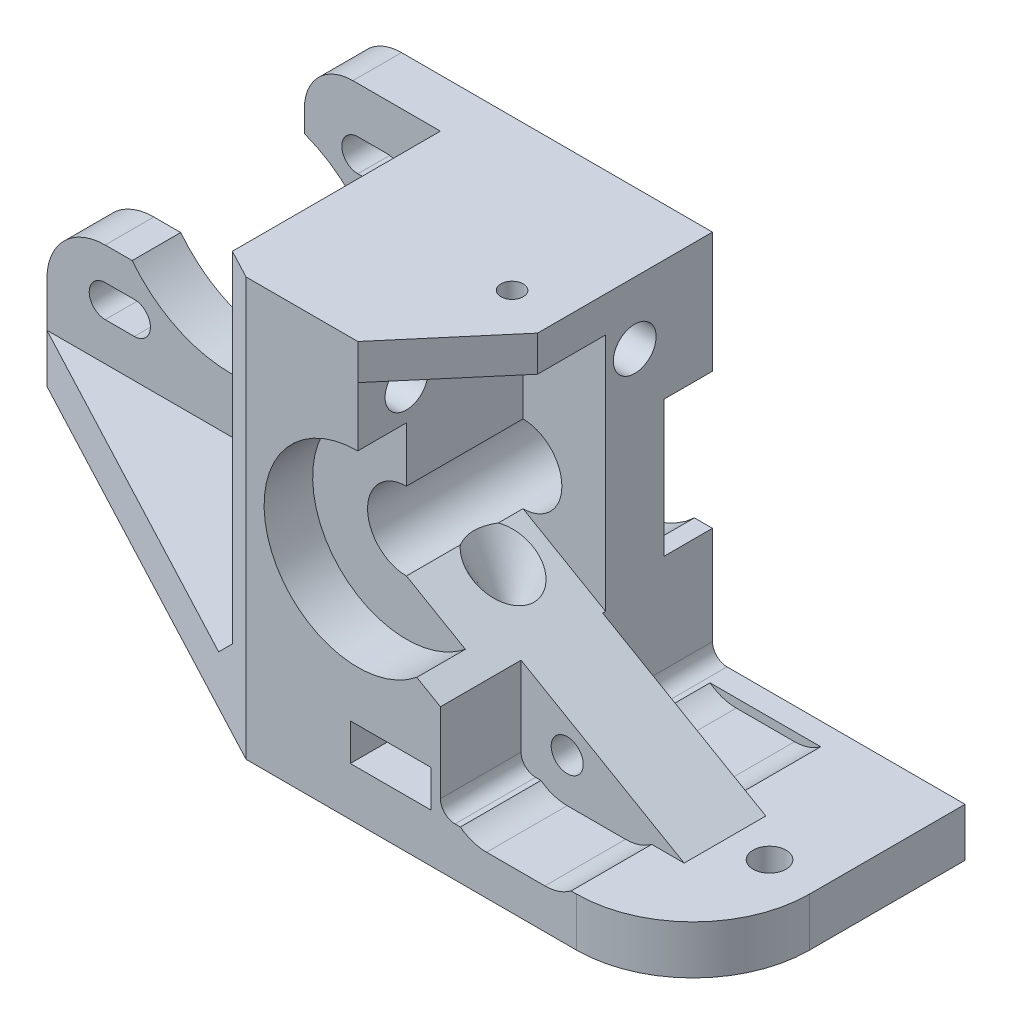
SolidWorks part; units mm, degrees
ref_plane "Front Plane" through (0, 0, 0) normal (0, 0, 1) x (1, 0, 0)
ref_plane "Top Plane" through (0, 0, 0) normal (0, 1, 0) x (1, 0, 0)
ref_plane "Right Plane" through (0, 0, 0) normal (1, 0, 0) x (0, 0, -1)
sketch "Sketch1" plane through (0, 0, 0) normal (0, 0, 1) x (1, 0, 0)
  line L0 (0, 0) -> (-60, 0) construction
  line L1 (-55, -23.6) -> (34.5, -23.6)
  line L2 (-55, -23.6) -> (-55, -8)
  line L3 (-28.5, 19.4) -> (34.5, 19.4)
  line L4 (34.5, -23.6) -> (34.5, 19.4)
  line L5 (-34.5, 0) -> (-34.5, -23.6) construction
  line L6 (-21.5, -17.6494) -> (-21.5, 14.65) construction
  line L7 (-20, 13) -> (-50, 13) construction
  line L8 (-23, 11.35) -> (-20, 11.35)
  line L9 (-23, 11.35) -> (-23, 14.65) construction
  line L10 (-23, 14.65) -> (-20, 14.65)
  line L11 (-20, 11.35) -> (-20, 14.65) construction
  line L12 (-36, -12.9851) -> (-33, -12.9851)
  line L14 (-20, -11.35) -> (-20, -14.65) construction
  line L15 (-23, -14.65) -> (-20, -14.65)
  line L16 (-23, -11.35) -> (-23, -14.65) construction
  line L17 (-23, -11.35) -> (-20, -11.35)
  line L18 (-46, -11.35) -> (-49, -11.35)
  line L19 (-46, -11.35) -> (-46, -14.65) construction
  line L20 (-46, -14.65) -> (-49, -14.65)
  line L21 (-49, -11.35) -> (-49, -14.65) construction
  line L26 (-28.5, 19.4) -> (-28.5, 12.1804)
  line L27 (-55, -8) -> (-46.228, -8)
  line L28 (-50, -13) -> (-19, -13) [skipped]
  line L29 (-47.5, 17.6494) -> (-47.5, -13.3506) [skipped]
  circle A0 centre (0, 0) radius 4
  circle A1 centre (-34.5, 0) radius 13 construction
  arc A2 (-46.228, -8) -> (-36, -12.9851) centre (-36, 0) ccw
  arc A3 (-20, 11.35) -> (-20, 14.65) centre (-20, 13) ccw
  arc A4 (-33, -12.9851) -> (-28.5, 12.1804) centre (-33, 0) ccw
  arc A5 (-23, 14.65) -> (-23, 11.35) centre (-23, 13) ccw
  arc A6 (-23, -11.35) -> (-23, -14.65) centre (-23, -13) ccw
  arc A7 (-20, -14.65) -> (-20, -11.35) centre (-20, -13) ccw
  arc A8 (-49, -11.35) -> (-49, -14.65) centre (-49, -13) ccw
  arc A9 (-46, -14.65) -> (-46, -11.35) centre (-46, -13) ccw
  dimension "D1" = 8
  dimension "D6" = 34.5
  dimension "D8" = 3.3
  dimension "D2" = 26
  dimension "D7" = 6
  dimension "D3" = 43
  dimension "D4" = 55
  dimension "D5" = 23.6
  dimension "D9" = 3
  dimension "D10" = 3
  dimension "D11" = 1.5
  dimension "D12" = 8
  dimension "D13" = 34.5
extrude "Boss-Extrude1" add sketch "Sketch1" along normal blind 28
sketch "Sketch2" plane through (0, 0, 28) normal (0, 0, 1) x (1, 0, 0)
  line L0 (-55, -8) -> (-55, -23.6) construction
  line L1 (-55, -18.6) -> (-14.5, -18.6)
  line L2 (-55, -18.6) -> (-55, 19.4)
  line L3 (-55, 19.4) -> (-14.5, 19.4)
  line L4 (-14.5, -18.6) -> (-14.5, 19.4)
  line L5 (34.5, 19.4) -> (-28.5, 19.4) construction
  line L6 (0, 0) -> (-55, 0) construction
  circle A0 centre (-34.5, 0) radius 17.3693 construction
  dimension "D1" = 20
  dimension "D2" = 18.6
  dimension "D3" = 34.5
extrude "Cut-Extrude1" cut sketch "Sketch2" against normal offset from surface (23 mm away) 5 up to face at (-21.5, -13, 0)
sketch "Sketch3" plane through (0, 0, 28) normal (0, 0, 1) x (1, 0, 0)
  circle A0 centre (0, 0) radius 9.65
  dimension "D1" = 19.3
extrude "Cut-Extrude2" cut sketch "Sketch3" against normal blind 5
ref_plane "Plane1" through (0, 0, 11) normal (0, 0, 1) x (1, 0, 0)
ref_plane "Plane2" through (0, -18.6, 0) normal (0, -1, 0) x (1, 0, 0)
ref_plane "Plane3" through (0, 0, 15.5) normal (0, 0, 1) x (1, 0, 0)
sketch "Sketch8" plane through (0, -23.6, 0) normal (0, -1, 0) x (1, 0, 0)
  circle A0 centre (3.375, 15.5) radius 1.15
  dimension "D1" = 2.3
  dimension "D2" = 3.375
  dimension "D3" = 15.5
extrude "Cut-Extrude7" cut sketch "Sketch8" against normal through all
chamfer "Chamfer1" distance 23 distance2 43.5 1 edges at (-55, -21.1, 28) first distance on face at (-55, -16.7333, 11)
sketch "Sketch9" plane through (34.5, 0, 0) normal (1, 0, 0) x (0, 0, -1)
  line L1 (-15.5, 23.65) -> (-15.5, -23.65) construction
  line L2 (0, 0) -> (-25.9492, 0) construction
  circle A0 centre (-8, 13) radius 2.2
  circle A1 centre (-23, 13) radius 2.2
  dimension "D1" = 4.4
  dimension "D2" = 7.5
  dimension "D3" = 13
  dimension "D4" = 7.5
extrude "Cut-Extrude8" cut sketch "Sketch9" against normal through all
sketch "Sketch10" plane through (-14.5, 0, 0) normal (-1, 0, 0) x (0, 0, 1)
  line L1 (5.1, 14.6743) -> (5.1, 11.3257)
  line L2 (5.1, 11.3257) -> (8, 9.6514)
  line L3 (8, 9.6514) -> (10.9, 11.3257)
  line L4 (10.9, 11.3257) -> (10.9, 14.6743)
  line L5 (10.9, 14.6743) -> (8, 16.3486)
  line L6 (8, 16.3486) -> (5.1, 14.6743)
  line L7 (25.9, 11.3257) -> (25.9, 14.6743)
  line L8 (25.9, 14.6743) -> (23, 16.3486)
  line L9 (23, 16.3486) -> (20.1, 14.6743)
  line L10 (20.1, 14.6743) -> (20.1, 11.3257)
  line L11 (20.1, 11.3257) -> (23, 9.6514)
  line L12 (23, 9.6514) -> (25.9, 11.3257)
  circle A0 centre (8, 13) radius 2.9 construction
  circle A1 centre (8, 13) radius 2.2 construction
  circle A2 centre (23, 13) radius 2.9 construction
  circle A5 centre (23, 13) radius 2.2 construction
  dimension "D1" = 5.8
extrude "Cut-Extrude9" cut sketch "Sketch10" against normal blind 4 and the other way blind 3
chamfer "Chamfer2" distance 3 angle 45 1 edges at (-14.5, -18.6, 15.7069)
sketch "Sketch16" plane through (0, 0, 28) normal (0, 0, 1) x (1, 0, 0)
  line L0 (-17.5, -18.6) -> (-55, -18.6) construction
  line L1 (34.5, 19.4) -> (8.5, 19.4)
  line L2 (34.5, 19.4) -> (34.5, -18.6)
  line L3 (34.5, -18.6) -> (8.5, -18.6)
  line L4 (8.5, 19.4) -> (8.5, -18.6)
  dimension "D1" = 8.5
extrude "Cut-Extrude12" cut sketch "Sketch16" against normal through all
sketch "Sketch4" plane through (0, 0, 0) normal (0, 0, -1) x (-1, 0, 0)
  line L0 (0, 0) -> (-36.3115, 0) construction
  line L1 (-36.3115, -7) -> (-6.6425, -7)
  line L2 (-36.3115, -7) -> (-36.3115, 7)
  line L4 (-36.3115, 7) -> (-6.6425, 7)
  line L5 (-36.3115, -7) -> (0, 5) construction
  line L6 (-1.3153, -8.4204) -> (-36.3115, 7) construction
  arc A0 (-6.6425, -7) -> (-6.6425, 7) centre (0, 0) ccw
  dimension "D1" = 19.3
  dimension "D2" = 14
extrude "Cut-Extrude3" cut sketch "Sketch4" against normal blind 5
fillet "Fillet6" radius 1.5 1 edges at (8.5, -18.6, 14)
sketch "Sketch17" plane through (0, 0, 28) normal (0, 0, 1) x (1, 0, 0)
  line L0 (8.5, 19.4) -> (8.5, 4.5686) construction
  line L1 (0, 0) -> (19.7064, 0) construction
  line L2 (0, 4) -> (0, -4) construction
  line L3 (0, 4) -> (0, 15.7335)
  line L4 (0, 15.7335) -> (8.5, 15.7335)
  line L6 (8.5, 15.7335) -> (8.5, -8.9075)
  line L7 (8.5, -8.9075) -> (0, -4)
  arc A2 (0, -4) -> (0, 4) centre (0, 0) ccw
  circle A4 centre (0, 0) radius 4 construction
  dimension "D1" = 120
extrude "Cut-Extrude13" cut sketch "Sketch17" against normal blind 17
ref_axis "Axis1" through (3.375, 19.4, 15.5) along (0, -1, 0)
sketch "Sketch20" plane through (0, 0, 15.5) normal (0, 0, 1) x (1, 0, 0)
  line L0 (3.375, -3.8) -> (3.375, -11.8) construction
  line L1 (3.375, 19.4) -> (3.375, 15.7335) construction
  line L2 (3.375, -11.8) -> (7.375, -3.8)
  line L3 (7.375, -3.8) -> (3.375, -3.8)
  line L4 (3.375, -3.8) -> (3.375, -11.8)
  dimension "D1" = 8
  dimension "D2" = 4
  dimension "D3" = 3.8
revolve "Cut-Revolve1" cut sketch "Sketch20" angle 360 about L0
sketch "Sketch21" plane through (0, 0, 15.5) normal (0, 0, 1) x (1, 0, 0)
  line L0 (14.7822, -11.8532) -> (7.25, -8.1858) construction
  line L1 (7.25, -8.1858) -> (7.25, -18.6)
  line L2 (7.25, -18.6) -> (25.2879, -18.6)
  line L3 (10, -18.6) -> (34.5, -18.6) construction
  line L4 (21.7997, -18.6) -> (15.7249, -12.5251) construction
  line L5 (6.0681, -7.5034) -> (8.5, -8.9075) construction
  line L6 (7.25, -8.1858) -> (25.2879, -18.6)
  line L7 (-15.4, -18.6) -> (15.4, -18.6) construction
  line L8 (0, -4) -> (6.0681, -7.5034) construction
  circle A0 centre (13.25, -15) radius 1.65
  arc A1 (15.7249, -12.5251) -> (14.7822, -11.8532) centre (13.25, -15) ccw construction
  point P13 (0, 0)
  dimension "D2" = 3.3
  dimension "D5" = 3.5
  dimension "D1" = 13.25
  dimension "D3" = 15
  dimension "D4" = 6
  dimension "D6" = 45
extrude "Boss-Extrude3" add sketch "Sketch21" against normal blind 4.2 and the other way blind 4.2
sketch "Sketch15" plane through (0, -23.6, 0) normal (0, -1, 0) x (1, 0, 0)
  line L0 (-20.625, 15) -> (29.375, 15) construction
  circle A1 centre (-20.625, 15) radius 1.7
  circle A2 centre (29.375, 15) radius 1.7
  circle A3 centre (3.375, 15.5) radius 1.15 construction
  point P4 (3.375, 15.5)
  dimension "D2" = 3.4
  dimension "D1" = 50
extrude "Cut-Extrude11" cut sketch "Sketch15" against normal through all
sketch "Sketch22" plane through (0, 0, 19.7) normal (0, 0, 1) x (1, 0, 0)
  line L0 (13.25, -19.5) -> (19.25, -19.5)
  line L3 (19.25, -10.5) -> (13.25, -10.5)
  arc A0 (13.25, -10.5) -> (13.25, -19.5) centre (13.25, -15) ccw
  circle A1 centre (13.25, -15) radius 1.65 construction
  arc A2 (19.25, -19.5) -> (19.25, -10.5) centre (19.25, -15) ccw
  dimension "D1" = 9
  dimension "D2" = 6
extrude "Cut-Extrude14" cut sketch "Sketch22" along normal blind 9
mirror "Mirror1" about plane through (0, 0, 15.5) normal (0, 0, 1) of "Cut-Extrude14"
chamfer "Chamfer4" distance 8.5 distance2 10 1 edges at (8.5, 17.5668, 28) first distance on face at (9.2891, -7.4521, 28)
fillet "Fillet1" radius 5 1 edges at (-28.5, 19.4, 2.5)
fillet "Fillet2" radius 6 1 edges at (-55, -8, 2.5)
fillet "Fillet4" radius 12 1 edges at (34.5, -21.1, 28)
sketch "Sketch23" plane through (0, -18.6, 0) normal (0, -1, 0) x (1, 0, 0)
  line L0 (-0.775, 28.722) -> (7.525, 28.722)
  line L3 (-0.775, 28.722) -> (-0.775, 13.104)
  line L4 (-0.775, 13.104) -> (3.375, 10.708)
  line L5 (3.375, 10.708) -> (7.525, 13.104)
  line L6 (7.525, 13.104) -> (7.525, 28.722)
  line L8 (3.375, 20.292) -> (-0.775, 17.896) [skipped]
  line L9 (7.525, 17.896) -> (3.375, 20.292) [skipped]
  circle A0 centre (3.375, 15.5) radius 4.25 construction
  dimension "D1" = 8.5
extrude "Cut-Extrude15" cut sketch "Sketch23" against normal blind 3.8
sketch "Sketch24" plane through (0, -23.6, 0) normal (0, -1, 0) x (1, 0, 0)
  line L0 (-10.475, 15.5) -> (17.225, 15.5) construction
  line L1 (23.65, 15.5) -> (-23.65, 15.5) construction
  circle A0 centre (3.375, 15.5) radius 12.5 construction
  circle A1 centre (-10.475, 15.5) radius 1.35
  circle A2 centre (17.225, 15.5) radius 1.35
  dimension "D1" = 25
  dimension "D2" = 2.7
extrude "Cut-Extrude16" [suppressed] cut sketch "Sketch24" against normal blind 10
sketch "Sketch25" [suppressed] plane through (0, -14.6, 0) normal (0, -1, 0) x (1, 0, 0)
  line L0 (-17.5, 18.4) -> (-17.5, 12.6)
  line L1 (20.125, 17.1743) -> (17.225, 18.8486)
  line L2 (17.225, 18.8486) -> (14.325, 17.1743)
  line L3 (14.325, 17.1743) -> (14.325, 13.8257)
  line L4 (14.325, 13.8257) -> (17.225, 12.1514)
  line L5 (17.225, 12.1514) -> (20.125, 13.8257)
  line L6 (20.125, 13.8257) -> (20.125, 17.1743)
  line L7 (-7.1264, 15.5) -> (-8.8007, 18.4)
  line L8 (-8.8007, 18.4) -> (-17.5, 18.4)
  line L9 (-17.5, 24.8276) -> (-17.5, 5) construction
  line L11 (-17.5, 12.6) -> (-8.8007, 12.6)
  line L12 (-8.8007, 12.6) -> (-7.1264, 15.5)
  line L14 (-13.8236, 15.5) -> (-12.1493, 12.6) [skipped]
  line L15 (-12.1493, 18.4) -> (-13.8236, 15.5) [skipped]
  circle A0 centre (17.225, 15.5) radius 2.9 construction
  circle A1 centre (-10.475, 15.5) radius 2.9 construction
  circle A2 centre (17.225, 15.5) radius 1.35 construction
  circle A3 centre (-10.475, 15.5) radius 1.35 construction
  dimension "D1" = 5.8
extrude "Cut-Extrude17" [suppressed] cut sketch "Sketch25" along normal blind 6 and the other way blind 3
sketch "Sketch26" plane through (0, -23.6, 0) normal (0, -1, 0) x (1, 0, 0)
  circle A0 centre (3.375, 15.5) radius 3.15
  circle A1 centre (3.375, 15.5) radius 1.15 construction
  dimension "D1" = 6.3
extrude "Cut-Extrude18" cut sketch "Sketch26" against normal up to next
